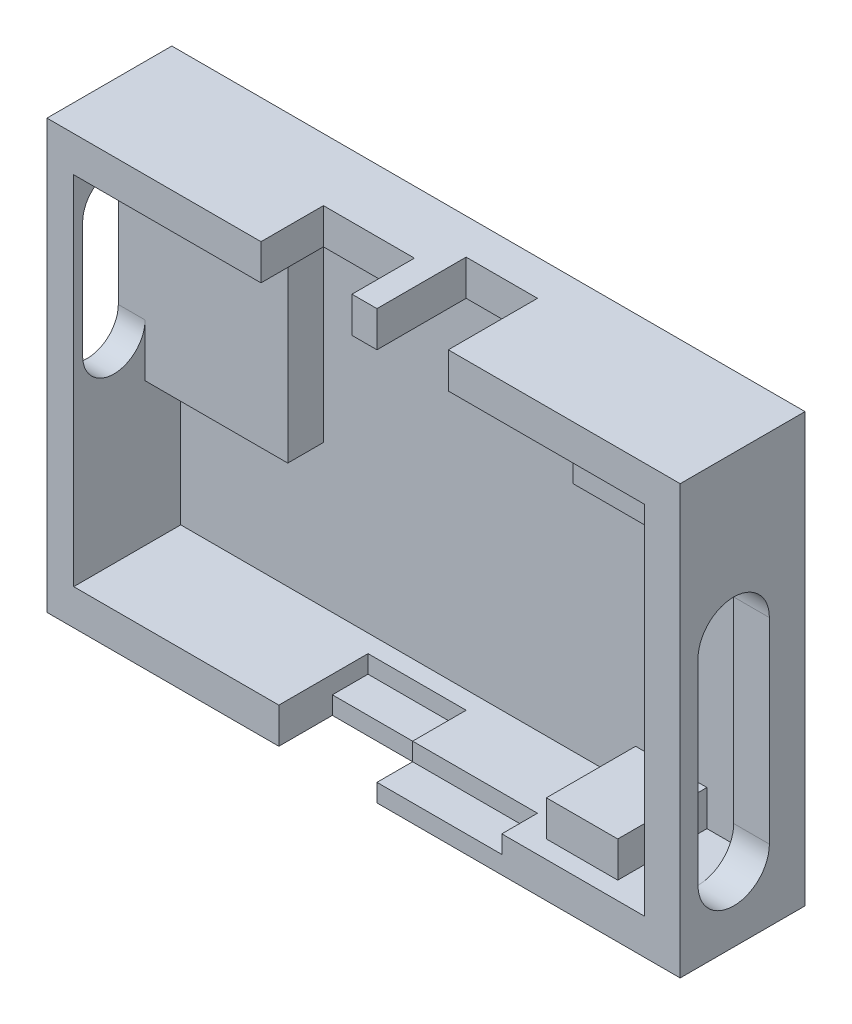
SolidWorks part; units mm, degrees
ref_plane "前视基准面" through (0, 0, 0) normal (0, 0, 1) x (1, 0, 0)
ref_plane "上视基准面" through (0, 0, 0) normal (0, 1, 0) x (1, 0, 0)
ref_plane "右视基准面" through (0, 0, 0) normal (1, 0, 0) x (0, 0, -1)
sketch "草图1" plane through (0, 0, 0) normal (0, 0, 1) x (1, 0, 0)
  line L5 (-17.75, 12) -> (17.75, 12)
  line L6 (-17.75, 12) -> (-17.75, -12)
  line L7 (-17.75, -12) -> (17.75, -12)
  line L8 (17.75, 12) -> (17.75, -12)
  line L9 (-17.75, 12) -> (17.75, -12) construction
  line L10 (-17.75, -12) -> (17.75, 12) construction
  point P0 (0, 0)
  dimension "D1" = 35.5
  dimension "D2" = 24
extrude "凸台-拉伸1" add sketch "草图1" along normal blind 7
sketch "草图2" plane through (0, 0, 7) normal (0, 0, 1) x (1, 0, 0)
  line L5 (-16.25, 11) -> (16.75, -11) construction
  line L6 (-16.25, -11) -> (16.75, 11) construction
  line L9 (-17.75, 12) -> (-17.75, -12) construction
  line L10 (-16.25, 11) -> (16.75, 11)
  line L11 (-16.25, 11) -> (-16.25, -11)
  line L12 (-16.25, -11) -> (16.75, -11)
  line L13 (16.75, 11) -> (16.75, -11)
  line L15 (17.75, 12) -> (-17.75, 12) construction
  line L16 (17.75, -12) -> (17.75, 12) construction
  point P0 (0, 0)
  dimension "D1" = 1.5
  dimension "D2" = 1
  dimension "D3" = 1
  dimension "D4" = 22
extrude "切除-拉伸1" cut sketch "草图2" against normal blind 6
sketch "草图3" plane through (-17.75, 0, 0) normal (-1, 0, 0) x (0, 0, 1)
  line L0 (4.75, 7.45) -> (4.75, 0.95) construction
  line L1 (6.5, 7.45) -> (6.5, 0.95)
  line L2 (3, 7.45) -> (3, 0.95)
  line L3 (0, 12) -> (0, -12) construction
  line L4 (7, 12) -> (0, 12) construction
  arc A0 (6.5, 7.45) -> (3, 7.45) centre (4.75, 7.45) ccw
  arc A1 (3, 0.95) -> (6.5, 0.95) centre (4.75, 0.95) ccw
  point P2 (4.75, 4.2)
  dimension "D3" = 6.5
  dimension "D4" = 4.55
  dimension "D1" = 3
  dimension "D2" = 3.5
extrude "切除-拉伸2" cut sketch "草图3" against normal blind 2
sketch "草图6" plane through (0, 0, 1) normal (0, 0, 1) x (1, 0, 0)
  line L14 (-16.25, 10) -> (15.75, 10)
  line L15 (-16.25, 11) -> (-16.25, -11) construction
  line L16 (15.75, 10) -> (15.75, -10)
  line L17 (15.75, -10) -> (-16.25, -10)
  line L18 (-16.25, -10) -> (-16.25, -11)
  line L19 (-16.25, -11) -> (16.75, -11)
  line L20 (16.75, -11) -> (16.75, 11)
  line L21 (16.75, 11) -> (-16.25, 11)
  line L22 (-16.25, 11) -> (-16.25, 10)
  dimension "D1" = 1
  dimension "D2" = 1
  dimension "D3" = 1
extrude "凸台-拉伸2" add sketch "草图6" along normal blind 6
sketch "草图7" plane through (0, 0, 1) normal (0, 0, 1) x (1, 0, 0)
  line L5 (9.25, -10) -> (13.25, -10)
  line L6 (9.25, -10) -> (9.25, -8)
  line L7 (9.25, -8) -> (13.25, -8)
  line L8 (13.25, -10) -> (13.25, -8)
  line L16 (15.75, 10) -> (15.75, -10) construction
  line L23 (15.75, 10) -> (10.75, 10)
  line L24 (15.75, 10) -> (15.75, 8)
  line L25 (15.75, 8) -> (10.75, 8)
  line L26 (10.75, 10) -> (10.75, 8)
  dimension "D1" = 2.5
  dimension "D3" = 5
  dimension "D4" = 2
  dimension "D5" = 4
  dimension "D8" = 2
extrude "凸台-拉伸3" add sketch "草图7" along normal blind 5
sketch "草图10" plane through (15.75, 0, 0) normal (-1, 0, 0) x (0, 0, 1)
  line L0 (4, -8) -> (4, 3) construction
  line L1 (2, -8) -> (2, 3)
  line L2 (6, -8) -> (6, 3)
  line L4 (7, -12) -> (0, -12) construction
  line L5 (7, -12) -> (7, 12) construction
  arc A0 (2, -8) -> (6, -8) centre (4, -8) ccw
  arc A1 (6, 3) -> (2, 3) centre (4, 3) ccw
  point P2 (4, -2.5)
  point P7 (4, 5)
  point P8 (4, -10)
  dimension "D2" = 15
  dimension "D1" = 11
  dimension "D3" = 1
  dimension "D4" = 2
extrude "切除-拉伸4" cut sketch "草图10" against normal blind 2
sketch "草图12" plane through (0, 0, 7) normal (0, 0, 1) x (1, 0, 0)
  line L8 (15.75, -10) -> (-16.25, -10) construction
  line L9 (-4.75, -10) -> (0.75, -10)
  line L10 (-4.75, -10) -> (-4.75, -11)
  line L11 (-4.75, -11) -> (0.75, -11)
  line L12 (0.75, -10) -> (0.75, -11)
  line L14 (-16.25, -10) -> (-16.25, 10) construction
  line L15 (-16.25, 10) -> (-16.25, -10) construction
  point P12 (0, 0)
  point P13 (0, 0)
  point P14 (0, 0)
  dimension "D1" = 11.5
  dimension "D2" = 17
extrude "切除-拉伸6" cut sketch "草图12" against normal blind 5
sketch "草图16" plane through (0, 10, 0) normal (0, -1, 0) x (1, 0, 0)
  line L0 (-16.25, 7) -> (15.75, 7) construction
  line L1 (-5.75, 7) -> (-0.65, 7)
  line L2 (-5.75, 7) -> (-5.75, 3.5)
  line L3 (-5.75, 3.5) -> (-0.65, 3.5)
  line L4 (-0.65, 7) -> (-0.65, 3.5)
  line L5 (-17.75, 7) -> (-17.75, 0) construction
  dimension "D1" = 12
  dimension "D2" = 17.1
  dimension "D3" = 3.5
extrude "切除-拉伸8" cut sketch "草图16" against normal blind 5
sketch "草图18" plane through (0, 0, 7) normal (0, 0, 1) x (1, 0, 0)
  line L0 (15.75, -10) -> (0.75, -10) construction
  line L1 (0.75, -11) -> (7.75, -11)
  line L2 (0.75, -11) -> (0.75, -10)
  line L3 (0.75, -10) -> (7.75, -10)
  line L4 (7.75, -11) -> (7.75, -10)
  point P7 (0, 0)
  dimension "D1" = 7
extrude "FPC排线间隙" cut sketch "草图18" against normal blind 2
sketch "草图19" plane through (0, 0, 1) normal (0, 0, 1) x (1, 0, 0)
  line L1 (-16.25, 10) -> (-8.25, 10)
  line L2 (-16.25, 10) -> (-16.25, -2)
  line L3 (-16.25, -2) -> (-8.25, -2)
  line L4 (-8.25, 10) -> (-8.25, -2)
  dimension "D1" = 8
  dimension "D2" = 12
extrude "USB支撑" add sketch "草图19" along normal blind 2
sketch "草图20" plane through (0, 12, 0) normal (0, 1, 0) x (1, 0, 0)
  line L1 (0.75, -2) -> (4.75, -2)
  line L2 (0.75, -2) -> (0.75, -7)
  line L3 (0.75, -7) -> (4.75, -7)
  line L4 (4.75, -2) -> (4.75, -7)
  line L5 (17.75, -7) -> (17.75, 0) construction
  line L6 (17.75, -7) -> (-0.65, -7) construction
  dimension "D1" = 4
  dimension "D2" = 5
  dimension "D3" = 0
  dimension "D4" = 13
extrude "切除-拉伸10" cut sketch "草图20" against normal blind 2
sketch "草图22" plane through (0, -11, 0) normal (0, 1, 0) x (1, 0, 0)
  line L0 (0.75, -2) -> (0.75, -5) construction
  line L1 (-4.75, -7) -> (0.75, -7)
  line L2 (-4.75, -7) -> (-4.75, -4)
  line L3 (-4.75, -4) -> (0.75, -4)
  line L4 (0.75, -7) -> (0.75, -4)
  dimension "D1" = 3
extrude "切除-拉伸11" cut sketch "草图22" against normal blind 2
